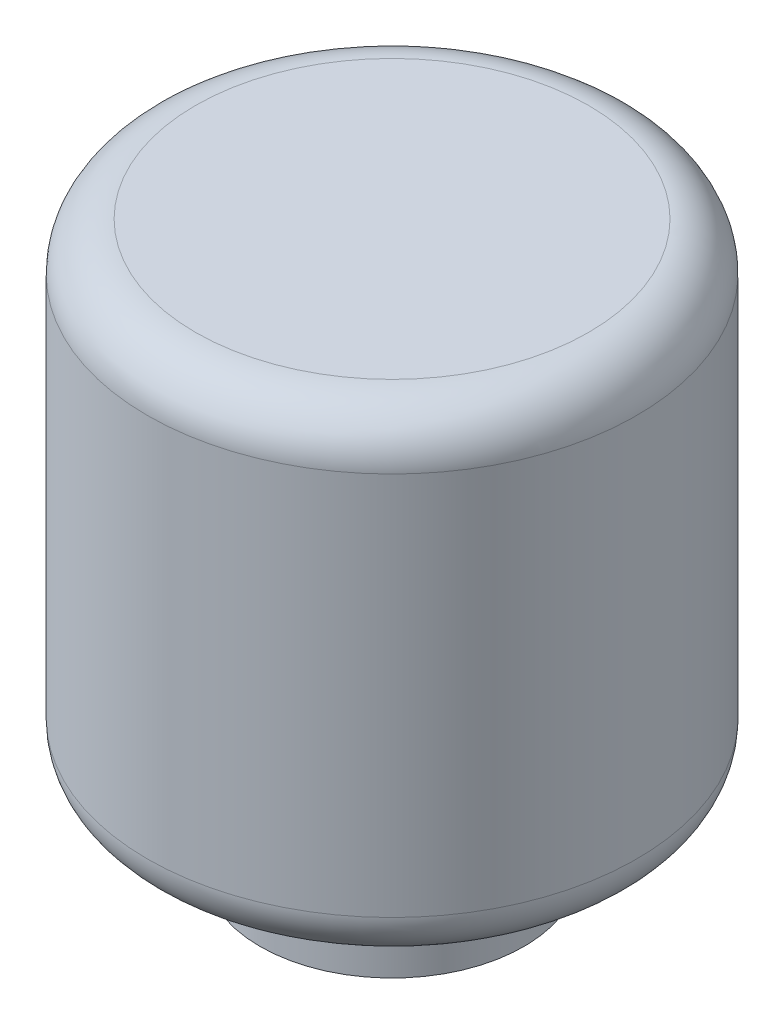
SolidWorks part; units mm, degrees
ref_plane "Front Plane" through (0, 0, 0) normal (0, 0, 1) x (1, 0, 0)
ref_plane "Top Plane" through (0, 0, 0) normal (0, 1, 0) x (1, 0, 0)
ref_plane "Right Plane" through (0, 0, 0) normal (1, 0, 0) x (0, 0, -1)
sketch "草图1" plane through (0, 0, 0) normal (0, 1, 0) x (1, 0, 0)
  circle A0 centre (0, 0) radius 5.5
extrude "凸台-拉伸1" add sketch "草图1" along normal blind 1.5
sketch "草图2" plane through (0, 1.5, 0) normal (0, 1, 0) x (1, 0, 0)
  circle A0 centre (0, 0) radius 2.5
extrude "凸台-拉伸2" add sketch "草图2" along normal blind 2
sketch "草图3" plane through (0, 3.5, 0) normal (0, 1, 0) x (1, 0, 0)
  circle A0 centre (0, 0) radius 10.1888
  point P9 (7.9991, 0)
extrude "凸台-拉伸3" add sketch "草图3" along normal blind 20
fillet "圆角2" radius 2 1 edges at (0, 23.5, 10.1888)
fillet "圆角3" radius 2 2 edges at (0, 3.5, 2.5) (0, 3.5, 10.1888)
scale "缩放比例1" scale about centroid uniform scaling yes scale factor 1.703704
